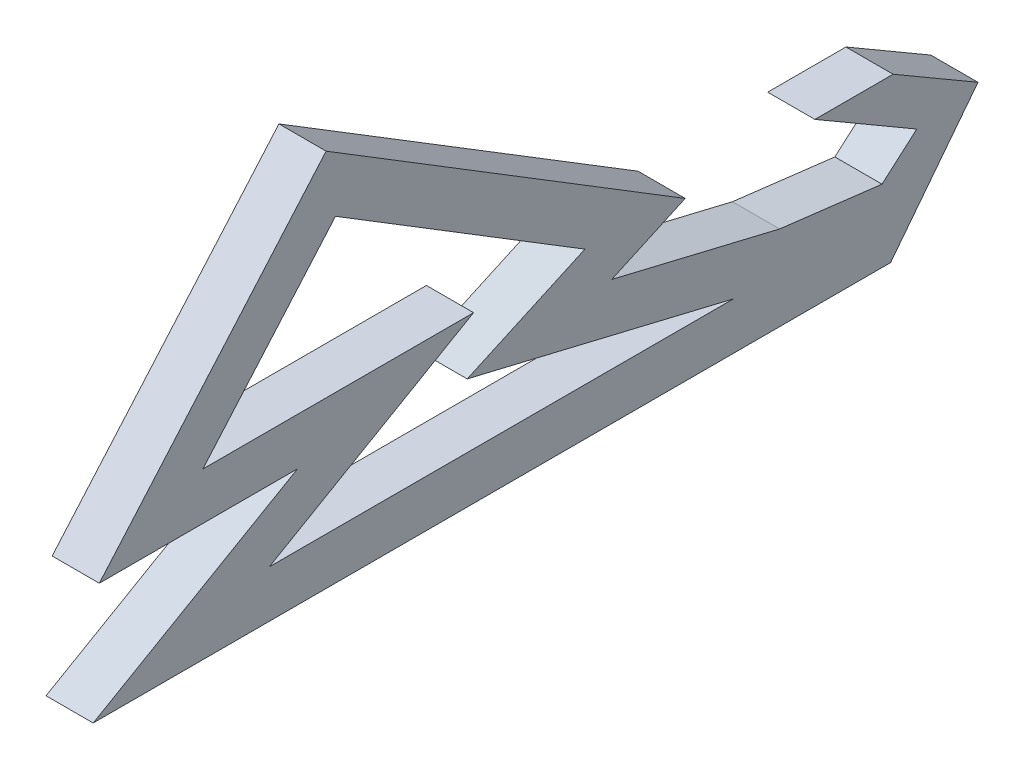
SolidWorks part; units mm, degrees
ref_plane "Front Plane" through (0, 0, 0) normal (0, 0, 1) x (1, 0, 0)
ref_plane "Top Plane" through (0, 0, 0) normal (0, 1, 0) x (1, 0, 0)
ref_plane "Right Plane" through (0, 0, 0) normal (1, 0, 0) x (0, 0, -1)
sketch "Sketch1" plane through (0, 0, 0) normal (1, 0, 0) x (0, 0, -1)
  line L0 (-84.5, 0) -> (84.5, 0)
  line L1 (-84.5, 0) -> (-41.1987, 25)
  line L2 (-41.1987, 25) -> (-83.1987, 25)
  line L4 (-35.1365, 80.2789) -> (40.974, 33.5461)
  line L5 (40.974, 33.5461) -> (25.3972, 26.4639)
  line L11 (103.0227, 23.8373) -> (84.5, 0)
  line L12 (19.7143, 34.8652) -> (-5.2375, 23.5205)
  line L13 (51.1954, 10) -> (-5.2375, 23.5205)
  line L15 (51.1954, 10) -> (51.1954, 10)
  line L16 (51.1954, 10) -> (51.1954, 10)
  line L17 (51.1954, 10) -> (51.1954, 10)
  line L18 (51.1954, 10) -> (51.1954, 10)
  line L19 (51.1954, 10) -> (51.1954, 10)
  line L29 (85.0303, 34.3106) -> (103.0227, 23.8373)
  line L30 (85.0303, 34.3106) -> (68.448, 34.3106)
  line L31 (68.448, 34.3106) -> (90.0408, 21.7416)
  line L32 (90.0408, 21.7416) -> (82.6811, 15.308)
  line L33 (-83.1987, 25) -> (-35.1365, 80.2789)
  line L34 (60.9814, 17.9384) -> (82.6811, 15.308)
  line L38 (60.9814, 17.9384) -> (25.3972, 26.4639)
  line L39 (51.1954, 10) -> (51.1954, 10)
  line L40 (-47.1795, 10) -> (51.1954, 10)
  line L41 (-47.1795, 10) -> (-3.8782, 35)
  line L42 (-3.8782, 35) -> (-61.253, 35)
  line L43 (-61.253, 35) -> (-33.149, 67.3239)
  line L44 (-33.149, 67.3239) -> (19.7143, 34.8652)
  point P4 (0, 0)
  dimension "D1" = 169
  dimension "D2" = 50
  dimension "D3" = 30
  dimension "D4" = 42
  dimension "D5" = 10
  dimension "D10" = 56
extrude "Boss-Extrude1" add sketch "Sketch1" along normal blind 10
